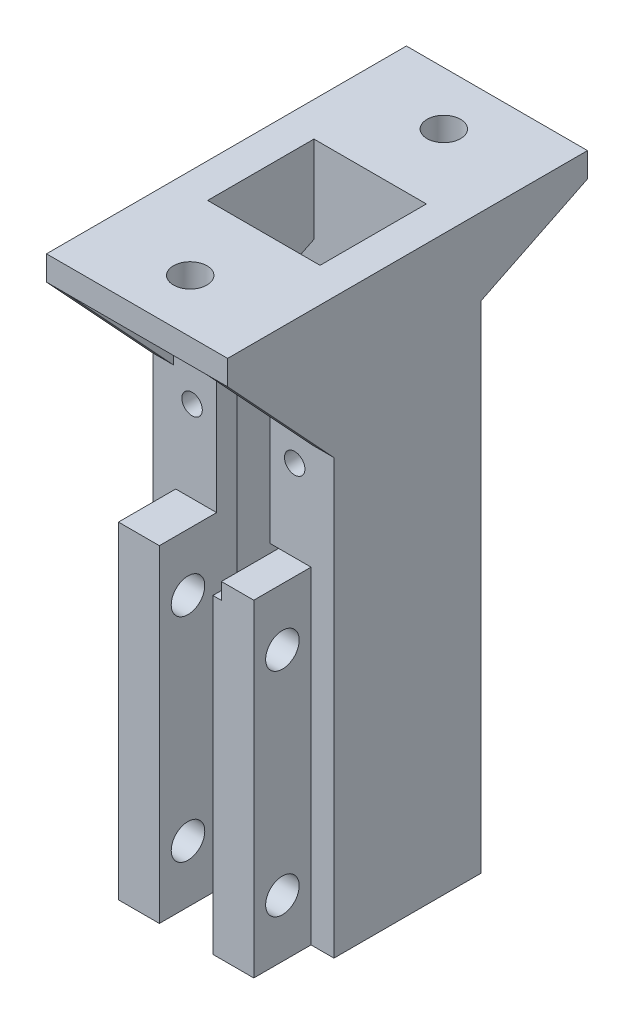
SolidWorks part; units mm, degrees
ref_plane "Front Plane" through (0, 0, 0) normal (0, 0, 1) x (1, 0, 0)
ref_plane "Top Plane" through (0, 0, 0) normal (0, 1, 0) x (1, 0, 0)
ref_plane "Right Plane" through (0, 0, 0) normal (1, 0, 0) x (0, 0, -1)
sketch "Sketch2" plane through (0, 0, 0) normal (0, 1, 0) x (1, 0, 0)
  line L0 (-15.5765, 2.3428) -> (6.5666, 2.3428)
  line L1 (-15.5765, 2.3428) -> (-15.5765, -0.1572)
  line L2 (6.5666, 2.3428) -> (6.5666, -0.1572)
  line L3 (-15.5765, -0.1572) -> (6.5666, -0.1572)
  line L4 (6.5666, 2.3428) -> (6.5666, -13.1572)
  line L5 (6.5666, 2.3428) -> (4.0666, 2.3428)
  line L6 (6.5666, -13.1572) -> (4.0666, -13.1572)
  line L7 (4.0666, 2.3428) -> (4.0666, -13.1572)
  line L8 (-15.5765, 2.3428) -> (-15.5765, -13.1572)
  line L9 (-15.5765, 2.3428) -> (-13.0765, 2.3428)
  line L10 (-15.5765, -13.1572) -> (-13.0765, -13.1572)
  line L11 (-13.0765, 2.3428) -> (-13.0765, -13.1572)
  line L12 (-15.5765, -13.1572) -> (-7.7765, -13.1572)
  line L13 (-15.5765, -13.1572) -> (-15.5765, -15.6572)
  line L14 (-7.7765, -13.1572) -> (-7.7765, -15.6572)
  line L15 (-15.5765, -15.6572) -> (-7.7765, -15.6572)
  line L16 (6.5666, -13.1572) -> (-1.2334, -13.1572)
  line L17 (6.5666, -13.1572) -> (6.5666, -15.6572)
  line L18 (-1.2334, -13.1572) -> (-1.2334, -15.6572)
  line L19 (6.5666, -15.6572) -> (-1.2334, -15.6572)
  line L20 (-7.7765, -15.6572) -> (-12.7765, -15.6572)
  line L21 (-7.7765, -15.6572) -> (-7.7765, -22.6572)
  line L22 (-12.7765, -15.6572) -> (-12.7765, -22.6572)
  line L23 (-7.7765, -22.6572) -> (-12.7765, -22.6572)
  line L24 (-1.2334, -15.6572) -> (3.7666, -15.6572)
  line L25 (-1.2334, -15.6572) -> (-1.2334, -22.6572)
  line L26 (3.7666, -15.6572) -> (3.7666, -22.6572)
  line L27 (-1.2334, -22.6572) -> (3.7666, -22.6572)
  point P0 (-7.9314, -0.1572)
  point P21 (4.0666, -0.1572)
  point P24 (4.0666, -13.1572)
  point P25 (-12.9001, -13.1572)
  point P26 (0, 0)
  dimension "D1" = 0
  dimension "D2" = 2.5
  dimension "D3" = 2.5
  dimension "D4" = 2.5
  dimension "D5" = 6.5431
  dimension "D6" = 360
  dimension "D7" = 13
  dimension "D8" = 2.5
  dimension "D9" = 2.5
  dimension "D10" = 13
  dimension "D11" = 5
  dimension "D12" = 5
  dimension "D13" = 90
  dimension "D14" = 7.8
  dimension "D15" = 7.8
  dimension "D16" = 16.9667
  dimension "D17" = 90
  dimension "D18" = 6.5431
  dimension "D19" = 7
  dimension "D20" = 7
extrude "Boss-Extrude1" add sketch "Sketch2" along normal blind 40 contours L16 L4 L2 L3 L7 | L9 L11 L3 L7 L5 L0 | L8 L12 L11 L3 L1 | L5 L7 L3 L2 | L11 L9 L1 L3 | L13 L15 L14 L12 L11 L10 | L12 L10 L11 | L6 L16 L7 | L19 L17 L6 L7 L16 L18 | L25 L27 L26 L19 | L23 L21 L15 L22 region at (-14.3265, 0, -1.0928) region at (-4.505, 0, -1.0928) region at (-14.3265, 0, 6.6572) region at (5.3166, 0, -1.0928) region at (-11.6765, 0, 14.4072) region at (5.3166, 0, 6.6572) region at (2.6666, 0, 14.4072) region at (-10.2765, 0, 19.1572) region at (1.2666, 0, 19.1572)
sketch "Sketch3" plane through (-12.7765, 0, 0) normal (-1, 0, 0) x (0, 0, 1)
  line L0 (22.6572, 40) -> (22.6572, 0) construction
  line L1 (15.6572, 40) -> (15.6572, 0) construction
  line L2 (15.6572, 40) -> (22.6572, 40) construction
  line L3 (15.6572, 0) -> (22.6572, 0) construction
  circle A0 centre (19.1572, 33) radius 2.05
  circle A1 centre (19.1572, 7) radius 2.05
  dimension "D5" = 4.1
  dimension "D6" = 4.1
  dimension "D1" = 3.5
  dimension "D2" = 3.5
  dimension "D3" = 3.5
  dimension "D4" = 3.5
  dimension "D7" = 7
  dimension "D8" = 7
extrude "Cut-Extrude2" cut sketch "Sketch3" against normal blind 40
sketch "Sketch26" plane through (0, 40, 0) normal (0, 1, 0) x (1, 0, 0)
  line L0 (3.7666, -15.6572) -> (6.5666, -15.6572)
  line L1 (6.5666, -15.6572) -> (6.5666, 2.3428)
  line L2 (6.5666, 2.3428) -> (-15.5765, 2.3428)
  line L3 (-15.5765, 2.3428) -> (-15.5765, -15.6572)
  line L4 (-15.5765, -15.6572) -> (-7.7765, -15.6572)
  line L5 (-7.7765, -13.1572) -> (-7.7765, -22.6572) construction
  line L6 (-7.7765, -15.6572) -> (-7.7765, -13.1572)
  line L7 (-7.7765, -13.1572) -> (-13.0765, -13.1572)
  line L8 (-13.0765, -13.1572) -> (-13.0765, -0.1572)
  line L9 (-13.0765, -0.1572) -> (4.0666, -0.1572)
  line L10 (4.0666, -0.1572) -> (4.0666, -13.1572)
  line L11 (4.0666, -13.1572) -> (-1.2334, -13.1572)
  line L12 (-1.2334, -13.1572) -> (-1.2334, -15.6572)
  line L13 (-1.2334, -13.1572) -> (-1.2334, -22.6572) construction
  line L14 (-1.2334, -15.6572) -> (3.7666, -15.6572)
  line L15 (3.7666, -15.6572) -> (3.6413, -15.6092)
  line M1 (-13.0765, -13.1572) -> (-13.0765, -0.1572)
  line M2 (-13.0765, -0.1572) -> (4.0666, -0.1572)
  line M3 (4.0666, -0.1572) -> (4.0666, -13.1572)
  line M4 (4.0666, -13.1572) -> (-1.2334, -13.1572)
  line M5 (-1.2334, -13.1572) -> (-1.2334, -22.6572)
  line M8 (3.7666, -15.6572) -> (6.5666, -15.6572)
  line M9 (6.5666, -15.6572) -> (6.5666, 2.3428)
  line M10 (6.5666, 2.3428) -> (-15.5765, 2.3428)
  line M11 (-15.5765, 2.3428) -> (-15.5765, -15.6572)
  line M12 (-15.5765, -15.6572) -> (-12.7765, -15.6572)
  line M15 (-7.7765, -22.6572) -> (-7.7765, -13.1572)
  line M16 (-7.7765, -13.1572) -> (-13.0765, -13.1572)
extrude "Boss-Extrude11" add sketch "Sketch26" along normal blind 30 contours L14 L4 M5 M8 M9 M10 M11 M12 M15 M16 M1 M2 M3 M4 region at (1.2666, 40, 15.3719)
sketch "Sketch7" plane through (0, 0, -2.3428) normal (0, 0, -1) x (-1, 0, 0)
  line L0 (-6.5666, 70) -> (-6.5666, 0) construction
  line L1 (4.6934, 38) -> (0.1934, 38)
  line L2 (4.6934, 38) -> (4.6934, 40)
  line L3 (4.6934, 40) -> (0.1934, 40)
  line L4 (0.1934, 38) -> (0.1934, 40)
  line L5 (15.5765, 70) -> (15.5765, 0) construction
  line L6 (15.5765, 0) -> (-6.5666, 0) construction
  point P4 (0.1934, 39)
  dimension "D1" = 6.76
  dimension "D2" = 4.5
  dimension "D3" = 2
  dimension "D4" = 10.8831
  dimension "D5" = 38
extrude "Cut-Extrude3" cut sketch "Sketch7" against normal through all
sketch "Sketch10" plane through (0, 0, -2.3428) normal (0, 0, -1) x (-1, 0, 0)
  line L0 (4.6934, 40) -> (0.1934, 40)
  line L1 (4.6934, 40) -> (4.6934, 115)
  line L2 (0.1934, 40) -> (0.1934, 115)
  line L3 (4.6934, 115) -> (0.1934, 115)
  dimension "D1" = 75
extrude "Cut-Extrude5" cut sketch "Sketch10" against normal blind 1.5
sketch "Sketch16" plane through (0, 0, 15.6572) normal (0, 0, 1) x (1, 0, 0)
  line L0 (-7.7765, 70) -> (-7.7765, 40) construction
  line L2 (-15.5765, 70) -> (-7.7765, 70) construction
  circle A0 centre (-10.7765, 50) radius 1.25
  dimension "D1" = 20
  dimension "D2" = 2.5
  dimension "D4" = 3
extrude "Cut-Extrude9" cut sketch "Sketch16" along direction (0, 0, 1) on the side against the normal blind 3.5
sketch "Sketch17" plane through (0, 0, 15.6572) normal (0, 0, 1) x (1, 0, 0)
  line L0 (-1.2334, 70) -> (-1.2334, 40) construction
  line L2 (-1.2334, 70) -> (6.5666, 70) construction
  circle A0 centre (1.7666, 50) radius 1.25
  dimension "D1" = 2.5
  dimension "D2" = 3
  dimension "D3" = 20
extrude "Cut-Extrude10" cut sketch "Sketch17" along direction (0, 0, 1) on the side against the normal blind 3.5
sketch "Sketch18" plane through (0, 0, 13.1572) normal (0, 0, -1) x (-1, 0, 0)
  line L1 (-6.5666, 70) -> (15.5765, 70)
  line L2 (-6.5666, 70) -> (-6.5666, 67)
  line L3 (-6.5666, 67) -> (15.5765, 67)
  line L4 (15.5765, 70) -> (15.5765, 67)
  line L6 (-6.5666, 70) -> (-6.5666, 0) construction
  line L8 (15.5765, 70) -> (7.7765, 70) construction
  point P4 (15.5765, 66.3874)
  point P5 (-9.9215, 70)
  point P6 (0, 0)
  point P7 (-8.2923, 66.5159)
  point P8 (12.2215, 66.9377)
  point P10 (12.2215, 65.6764)
  point P11 (-9.9215, 70)
  point P12 (12.2215, 65.9548)
  point P13 (15.5765, 70)
  point P14 (-6.6593, 66.9976)
  point P15 (-3.5403, 66.9549)
  point P16 (0, 0)
  point P17 (0, 0)
  point P20 (0, 0)
  point P21 (0, 0)
  point P22 (15.5765, 70)
  point P23 (15.2239, 69.2658)
  point P25 (-6.5666, 68.0626)
  dimension "D1" = 0
  dimension "D2" = 0
  dimension "D3" = 3
  dimension "D4" = 0
extrude "Boss-Extrude4" add sketch "Sketch18" against normal blind 15.5
sketch "Sketch19" plane through (0, 0, -2.3428) normal (0, 0, -1) x (-1, 0, 0)
  line L0 (-6.5666, 70) -> (-6.5666, 0) construction
  line L1 (15.5765, 70) -> (-6.5666, 70)
  line L2 (15.5765, 70) -> (15.5765, 67)
  line L3 (15.5765, 67) -> (-6.5666, 67)
  line L4 (-6.5666, 70) -> (-6.5666, 67)
  dimension "D1" = 3
extrude "Boss-Extrude5" add sketch "Sketch19" along normal blind 13 and the other way blind 2 contours L1 L4 L3 L2
sketch "Sketch21" plane through (-15.5765, 0, 0) normal (-1, 0, 0) x (0, 0, 1)
  line L0 (28.6572, 67) -> (15.6572, 53)
  line L1 (15.6572, 67) -> (15.6572, 0) construction
  line L2 (15.6572, 53) -> (15.6572, 67)
  line L3 (15.6572, 67) -> (28.6572, 67)
  dimension "D1" = 14
extrude "Boss-Extrude6" add sketch "Sketch21" against normal blind 2.5
sketch "Sketch22" plane through (6.5666, 0, 0) normal (1, 0, 0) x (0, 0, -1)
  line L0 (-28.6572, 67) -> (-15.6572, 67)
  line L1 (-15.6572, 67) -> (-15.6572, 53)
  line L2 (-15.6572, 67) -> (-15.6572, 0) construction
  line L3 (-15.6572, 53) -> (-28.6572, 67)
  dimension "D1" = 14
extrude "Boss-Extrude8" add sketch "Sketch22" against normal blind 2.5
sketch "Sketch23" plane through (6.5666, 0, 0) normal (1, 0, 0) x (0, 0, -1)
  line L0 (-13.1572, 70) -> (-13.1572, 53)
  line L2 (15.3428, 70) -> (15.3428, 67)
  line L3 (15.3428, 70) -> (-13.1572, 70)
  line L4 (15.3428, 67) -> (-13.1572, 53)
  dimension "D1" = 28.5
  dimension "D2" = 28.5
  dimension "D3" = 17
  dimension "D4" = 3
  dimension "D5" = 90
extrude "Boss-Extrude9" add sketch "Sketch23" against normal blind 4.2
sketch "Sketch24" plane through (-15.5765, 0, 0) normal (-1, 0, 0) x (0, 0, 1)
  line L0 (13.1572, 70) -> (-15.3428, 70)
  line L1 (-15.3428, 70) -> (-15.3428, 67)
  line L2 (-15.3428, 67) -> (13.1572, 53)
  line L4 (13.1572, 53) -> (13.1572, 70)
  line L5 (-15.3428, 70) -> (-15.3428, 67) construction
  point P3 (0, 0)
  dimension "D1" = 17
  dimension "D2" = 28.5
  dimension "D3" = 3
  dimension "D4" = 90
  dimension "D5" = 0
extrude "Boss-Extrude10" add sketch "Sketch24" against normal blind 4.2
sketch "Sketch25" plane through (0, 70, 0) normal (0, 1, 0) x (1, 0, 0)
  line L0 (-11.3765, 15.3428) -> (-11.3765, 2.3428) construction
  circle A0 centre (-4.505, 8.8428) radius 2.05
  circle A1 centre (-4.505, -22.1572) radius 2.05
  dimension "D1" = 4.1
  dimension "D2" = 4.1
  dimension "D7" = 6.8715
extrude "Cut-Extrude12" cut sketch "Sketch25" against normal blind 3.5
